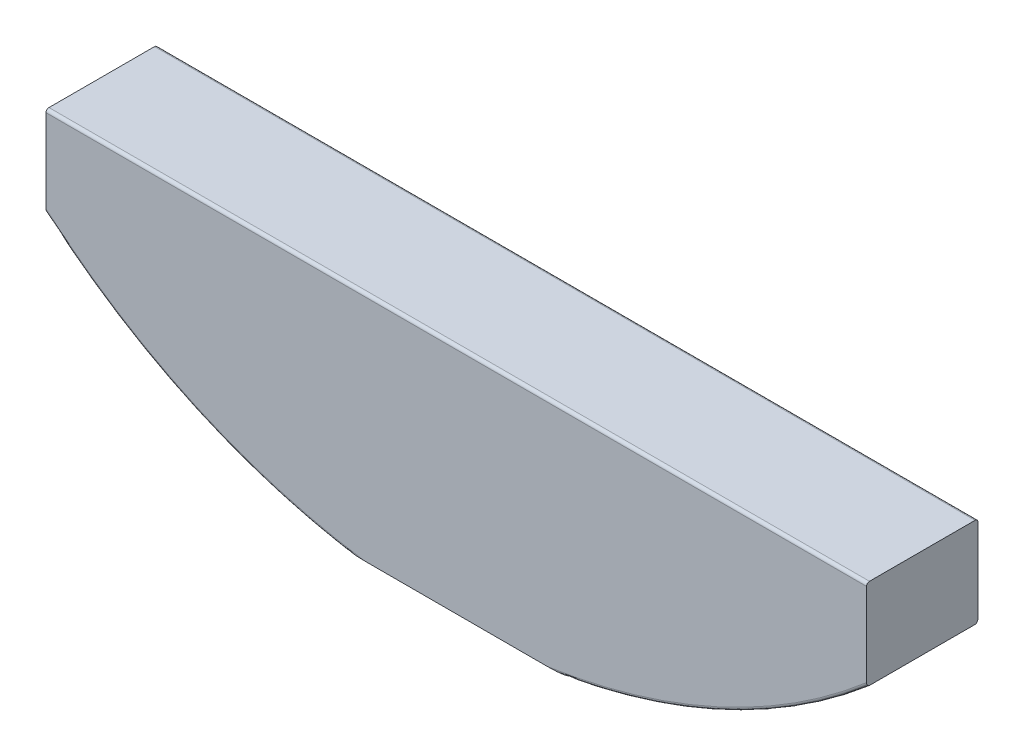
SolidWorks part; units mm, degrees
ref_plane "Front Plane" through (0, 0, 0) normal (0, 0, 1) x (1, 0, 0)
ref_plane "Top Plane" through (0, 0, 0) normal (0, 1, 0) x (1, 0, 0)
ref_plane "Right Plane" through (0, 0, 0) normal (1, 0, 0) x (0, 0, -1)
sketch "Sketch1" plane through (0, 0, 0) normal (0, 0, 1) x (1, 0, 0)
  line L0 (-73.722, 0) -> (74.6512, 0) construction
  line L1 (-21.2245, -16.6687) -> (21.2245, -16.6687)
  arc A0 (-21.2245, -16.6687) -> (21.2245, -16.6687) centre (0, 0) ccw
  dimension "Breadth" = 53.975
  dimension "Excursion" = 16.6687
extrude "Extrude1" add sketch "Sketch1" along normal blind 4.7625
fillet "Fillet3" radius 0.127 6 edges at (21.2245, -16.6687, 2.3813) (-21.2245, -16.6687, 2.3813) (0, -16.6687, 4.7625) (0, -26.9875, 4.7625) (0, -16.6687, 0) (0, -26.9875, 0)
sketch "Sketch3" plane through (0, 0, 0) normal (0, 0, 1) x (1, 0, 0)
  line L0 (-50.8, -26.5748) -> (50.8, -26.5748)
  line L2 (-20.9616, -16.6687) -> (20.9616, -16.6687) construction
  dimension "D1" = 50.8
  dimension "D2" = 101.6
  dimension "High" = 9.906
extrude "Cut-Extrude2" cut sketch "Sketch3" along normal through all and the other way through all flip side to cut
sketch "Sketch2" plane through (0, 0, 0) normal (0, 0, 1) x (1, 0, 0)
  line L0 (-17.526, 0) -> (-17.526, -50.8)
  line L1 (0, 0) -> (0, -50.8) construction
  dimension "D1" = 50.8
  dimension "Length" = 35.052
extrude "Cut-Extrude1" cut sketch "Sketch2" against normal through all and the other way through all flip side to cut
mirror "Mirror1" about plane through (0, 0, 0) normal (1, 0, 0) of "Cut-Extrude1"
equation "\"Radius@Fillet3\" = \"Width@Extrude1\"*2/75"
